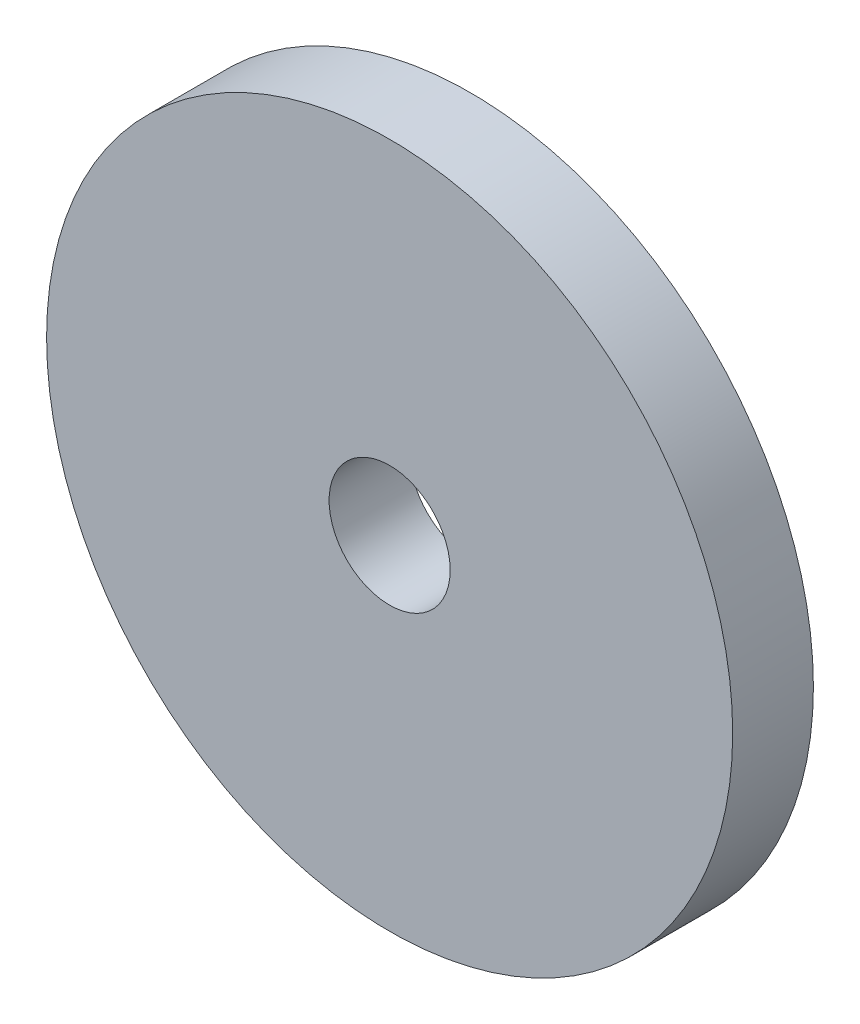
SolidWorks part; units mm, degrees
material "Acrylic (Medium-high impact)"
ref_plane "Front Plane" through (0, 0, 0) normal (0, 0, 1) x (1, 0, 0)
ref_plane "Top Plane" through (0, 0, 0) normal (0, 1, 0) x (1, 0, 0)
ref_plane "Right Plane" through (0, 0, 0) normal (1, 0, 0) x (0, 0, -1)
sketch "Model" plane through (0, 0, 0) normal (0, 0, 1) x (1, 0, 0)
  circle A0 centre (0, 0) radius 8.5
  circle A1 centre (0, 0) radius 1.5
  dimension "D1" = 17
  dimension "D2" = 3
extrude "Boss-Extrude1" add sketch "Model" along normal blind 2
